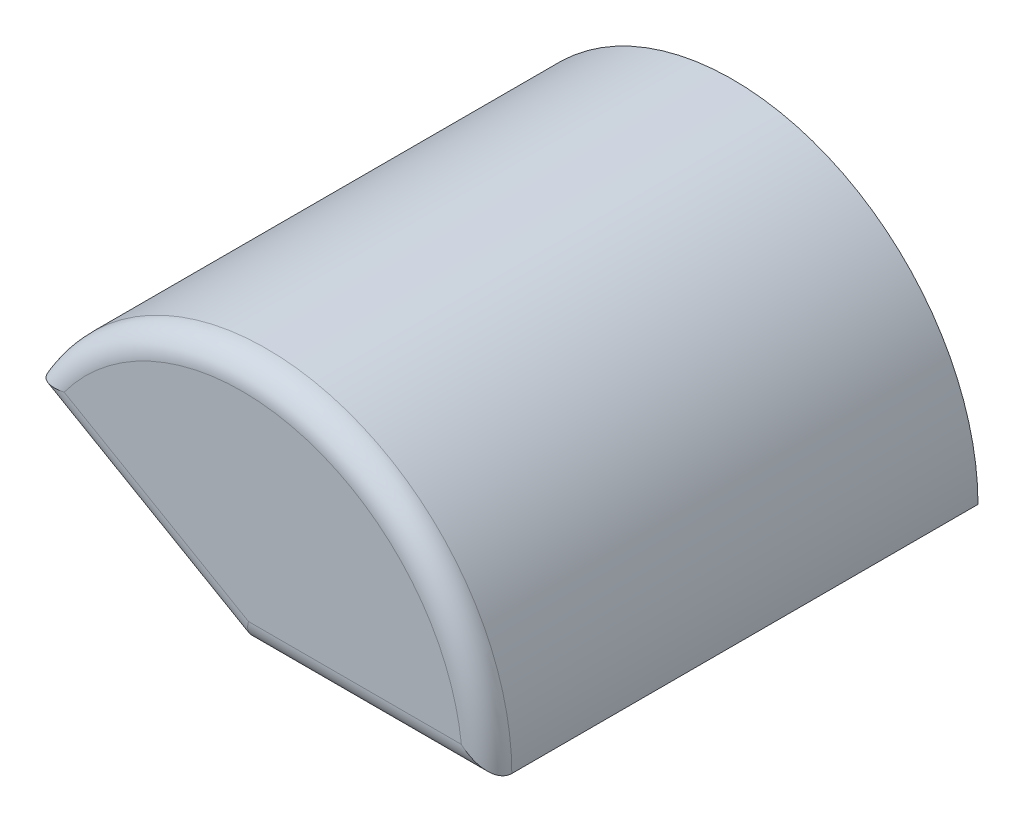
SolidWorks part; units mm, degrees
ref_plane "Front Plane" through (0, 0, 0) normal (0, 0, 1) x (1, 0, 0)
ref_plane "Top Plane" through (0, 0, 0) normal (0, 1, 0) x (1, 0, 0)
ref_plane "Right Plane" through (0, 0, 0) normal (1, 0, 0) x (0, 0, -1)
sketch "Sketch1" plane through (0, 0, 0) normal (0, 0, 1) x (1, 0, 0)
  line L0 (-8.6603, 5) -> (0, 0)
  line L1 (0, 0) -> (10, 0)
  arc A0 (10, 0) -> (-8.6603, 5) centre (0, 0) ccw
  dimension "D1" = 150
  dimension "D2" = 10
extrude "Boss-Extrude1" add sketch "Sketch1" along normal blind 20
fillet "Fillet1" radius 1 3 edges at (-4.3301, 2.5, 20) (2.5882, 9.6593, 20) (5, 0, 20)
equation "\"angle\"=150"
equation "\"thicknes\"=20"
equation "\"diameter\"=10"
equation "\"D1@Sketch1\"= \"angle\""
equation "\"D2@Sketch1\"= \"diameter\""
equation "\"D1@Boss-Extrude1\"= \"thicknes\""
